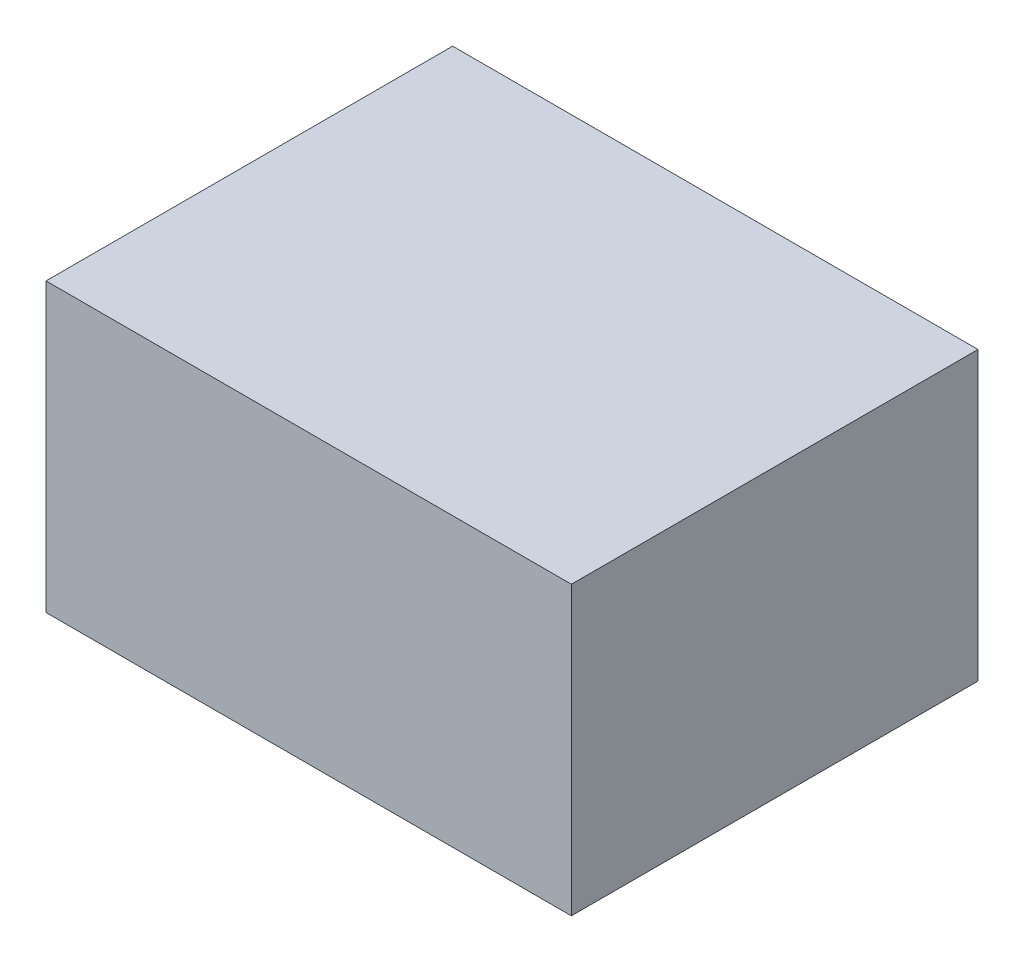
SolidWorks part; units mm, degrees
ref_plane "Front Plane" through (0, 0, 0) normal (0, 0, 1) x (1, 0, 0)
ref_plane "Top Plane" through (0, 0, 0) normal (0, 1, 0) x (1, 0, 0)
ref_plane "Right Plane" through (0, 0, 0) normal (1, 0, 0) x (0, 0, -1)
ref_plane "PL_Body_base" through (0, 0, -35) normal (0, 0, 1) x (1, 0, 0)
sketch "SK_Body" plane through (0, 0, -35) normal (0, 0, 1) x (1, 0, 0)
  line L0 (-12.5, -12.36) -> (32.72, -12.36)
  line L1 (32.72, -12.36) -> (32.72, 12.36)
  line L2 (32.72, 12.36) -> (-12.5, 12.36)
  line L3 (-12.5, 12.36) -> (-12.5, -12.36)
  dimension "P1" = 12.5
  dimension "P2" = 12.36
  dimension "P3" = 32.72
  dimension "P4" = 12.36
  dimension "P5" = 32.72
  dimension "P6" = 12.36
  dimension "P7" = 12.5
  dimension "P8" = 12.36
extrude "Body" add sketch "SK_Body" along normal blind 35
ref_axis "AX_Joint" through (0, 0, -36.75) along (0, 0, 1)
